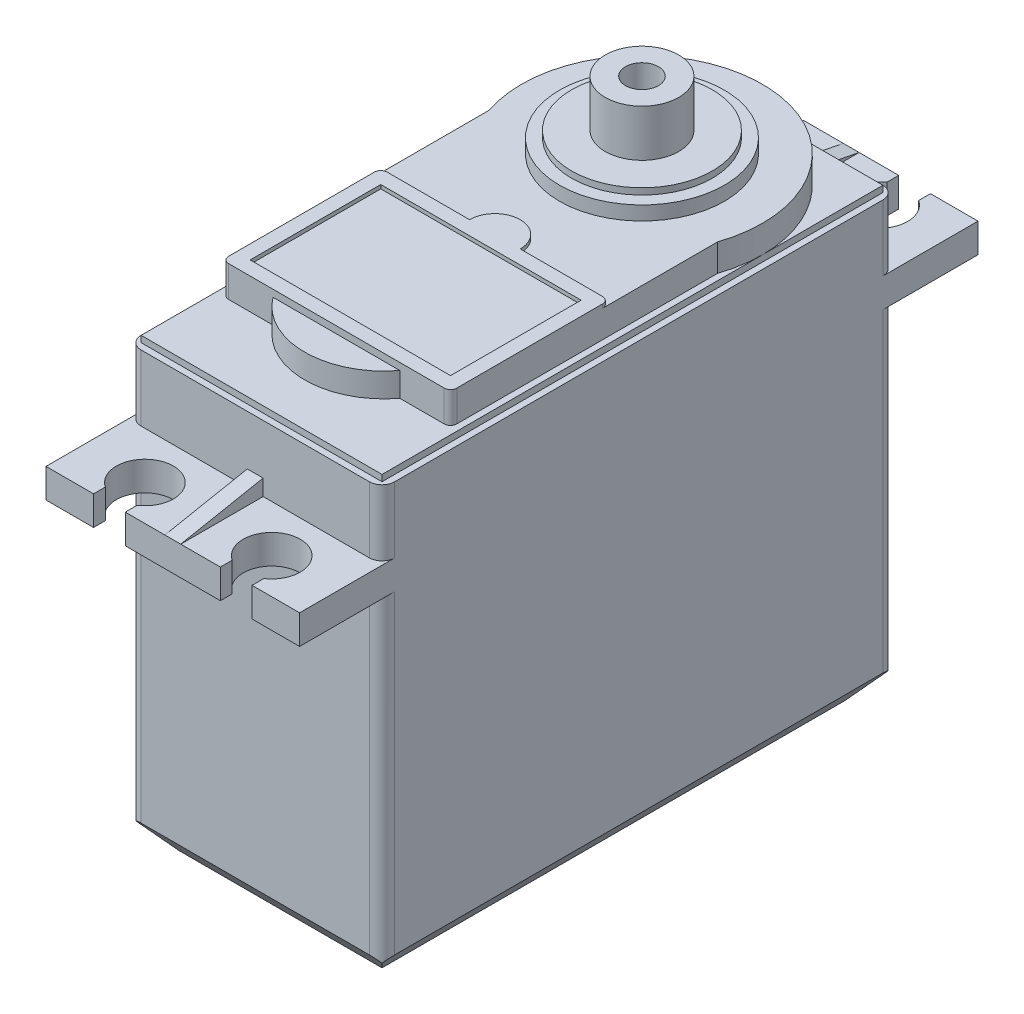
SolidWorks part; units mm, degrees
ref_plane "Front Plane" through (0, 0, 0) normal (0, 0, 1) x (1, 0, 0)
ref_plane "Top Plane" through (0, 0, 0) normal (0, 1, 0) x (1, 0, 0)
ref_plane "Right Plane" through (0, 0, 0) normal (1, 0, 0) x (0, 0, -1)
sketch "Sketch1" plane through (0, 0, 0) normal (0, 1, 0) x (1, 0, 0)
  line L0 (0, 0) -> (0, 10) construction
  line L1 (10, 10) -> (-10, 10)
  line L2 (10, 10) -> (10, -30.5)
  line L3 (10, -30.5) -> (-10, -30.5)
  line L4 (-10, 10) -> (-10, -30.5)
  dimension "D1" = 20
  dimension "D2" = 40.5
  dimension "D3" = 10
extrude "Boss-Extrude1" add sketch "Sketch1" along normal blind 35.2
chamfer "Chamfer1" distance 2 angle 50 4 edges at (0, 0, -10) (-10, 0, 10.25) (0, 0, 30.5) (10, 0, 10.25) first distance on face at (0, 0, 10.25)
ref_plane "Plane1" through (0, 27.2, 0) normal (0, 1, 0) x (-1, 0, 0)
sketch "Sketch2" plane through (0, 27.2, 0) normal (0, 1, 0) x (-1, 0, 0)
  line L0 (-10, 30.5) -> (-10, -10) construction
  line L1 (10, -10) -> (-10, -10)
  line L2 (10, -10) -> (10, -16.5)
  line L3 (10, -16.5) -> (6.25, -16.5)
  line L4 (-10, -10) -> (-10, -16.5)
  line L5 (5, -13.7) -> (-5, -13.7) construction
  line L6 (0, -10) -> (0, -13.7) construction
  line L7 (6.25, -16.5) -> (6.25, -15.5708)
  line L8 (3.75, -16.5) -> (3.75, -15.5708)
  line L9 (-3.75, -15.5708) -> (-3.75, -16.5)
  line L10 (3.75, -16.5) -> (-3.75, -16.5)
  line L11 (-6.25, -15.5708) -> (-6.25, -16.5)
  line L12 (-6.25, -16.5) -> (-10, -16.5)
  line L13 (10, 10.25) -> (-10, 10.25) construction
  line L14 (10, -10) -> (10, 30.5) construction
  line L15 (0, 30.5) -> (0, 34.2) construction
  line L16 (5, 34.2) -> (-5, 34.2) construction
  line L17 (-6.25, 37) -> (-10, 37)
  line L18 (-6.25, 36.0708) -> (-6.25, 37)
  line L19 (3.75, 37) -> (-3.75, 37)
  line L20 (-3.75, 36.0708) -> (-3.75, 37)
  line L21 (3.75, 37) -> (3.75, 36.0708)
  line L22 (6.25, 37) -> (6.25, 36.0708)
  line L23 (-10, 30.5) -> (-10, 37)
  line L24 (10, 37) -> (6.25, 37)
  line L25 (10, 30.5) -> (10, 37)
  line L26 (10, 30.5) -> (-10, 30.5)
  arc A0 (6.25, -15.5708) -> (3.75, -15.5708) centre (5, -13.7) ccw
  arc A1 (-3.75, -15.5708) -> (-6.25, -15.5708) centre (-5, -13.7) ccw
  arc A2 (-3.75, 36.0708) -> (-6.25, 36.0708) centre (-5, 34.2) cw
  arc A3 (6.25, 36.0708) -> (3.75, 36.0708) centre (5, 34.2) cw
  dimension "D2" = 4.5
  dimension "D1" = 10
  dimension "D3" = 2.8
  dimension "D4" = 6.5
  dimension "D5" = 2.5
extrude "Boss-Extrude2" add sketch "Sketch2" along normal blind 2.3
sketch "Sketch3" plane through (0, 29.5, 0) normal (0, 1, 0) x (1, 0, 0)
  line L0 (10, -30.5) -> (-10, -30.5) construction
  line L1 (0.625, -30.5) -> (-0.625, -30.5)
  line L2 (0.625, -30.5) -> (0.625, -37)
  line L3 (0.625, -37) -> (-0.625, -37)
  line L4 (-0.625, -30.5) -> (-0.625, -37)
  line L5 (-3.75, -37) -> (3.75, -37) construction
  line L6 (-10, 10) -> (10, 10) construction
  line L7 (-0.625, 10) -> (0.625, 10)
  line L8 (-0.625, 10) -> (-0.625, 16.5)
  line L9 (-0.625, 16.5) -> (0.625, 16.5)
  line L10 (0.625, 10) -> (0.625, 16.5)
  line L11 (3.75, 16.5) -> (-3.75, 16.5) construction
  line L12 (0, -30.5) -> (0, 0) construction
  line L13 (0, 0) -> (0, 10) construction
  dimension "D1" = 1.25
extrude "Boss-Extrude3" add sketch "Sketch3" along normal blind 1.3
chamfer "Chamfer2" distance 1.3 angle 79 2 edges at (0, 30.8, 37) (0, 30.8, -16.5) first distance on face at (0, 29.25, 37) first distance on face at (0, 29.25, -16.5)
sketch "Sketch5" plane through (0, 35.2, 0) normal (0, 1, 0) x (1, 0, 0)
  line L1 (-9.5, 9.5) -> (9.5, 9.5)
  line L2 (-9.5, 9.5) -> (-9.5, -30)
  line L3 (-9.5, -30) -> (9.5, -30)
  line L4 (9.5, 9.5) -> (9.5, -30)
  line L5 (-10, 10) -> (-9.5, 9.5) construction
  line L6 (10, 10) -> (-10, 10) construction
  line L7 (10, -30.5) -> (9.5, -30) construction
  line L8 (10, 10) -> (9.5, 9.5) construction
  line L9 (10, -30.5) -> (10, 10) construction
  line L10 (-9.5, -30) -> (-10, -30.5) construction
  line L11 (-10, 10) -> (-10, -30.5) construction
  line L13 (-10, -30.5) -> (10, -30.5) construction
  dimension "D1" = 0.5
  dimension "D2" = 0.5
  dimension "D3" = 0.5
  dimension "D4" = 0.5
extrude "Cut-Extrude1" cut sketch "Sketch5" against normal blind 0.5 flip side to cut
sketch "Sketch6" plane through (0, 35.2, 0) normal (0, 1, 0) x (1, 0, 0)
  line L0 (9.5, 9.5) -> (-9.5, 9.5) construction
  line L3 (-9, -3.0414) -> (-9, -24.1)
  line L4 (-9, -24.1) -> (9, -24.1)
  line L5 (9, -3.0414) -> (9, -24.1)
  arc A0 (9, -3.0414) -> (-9, -3.0414) centre (0, 0) ccw
  dimension "D1" = 18
  dimension "D2" = 24.1
extrude "Boss-Extrude4" add sketch "Sketch6" along normal blind 2.15
sketch "Sketch7" plane through (0, 35.2, 0) normal (0, 1, 0) x (1, 0, 0)
  line L0 (-9, -24.1) -> (9, -24.1) construction
  line L1 (-9, -24.1) -> (9, -24.1) construction
  line L2 (-5, -24.1) -> (5, -24.1)
  line L3 (0, -24.1) -> (0, -20.35) construction
  line L4 (0, -20.35) -> (0, 0) construction
  arc A0 (-5, -24.1) -> (5, -24.1) centre (0, -20.35) ccw
  point P8 (0, -26.6)
  dimension "D1" = 10
  dimension "D2" = 2.5
extrude "Boss-Extrude5" add sketch "Sketch7" along normal blind 1.9
sketch "Sketch8" plane through (0, 37.35, 0) normal (0, 1, 0) x (1, 0, 0)
  circle A0 centre (0, 0) radius 6.5
  dimension "D1" = 13
extrude "Boss-Extrude6" add sketch "Sketch8" along normal blind 1.1
sketch "Sketch9" plane through (0, 38.45, 0) normal (0, 1, 0) x (1, 0, 0)
  circle A0 centre (0, 0) radius 5.55
  dimension "D1" = 11.1
extrude "Boss-Extrude7" add sketch "Sketch9" along normal blind 0.5
sketch "Sketch10" plane through (0, 38.95, 0) normal (0, 1, 0) x (1, 0, 0)
  circle A0 centre (0, 0) radius 2.9
  circle A1 centre (0, 0) radius 1.3
  dimension "D1" = 5.8
  dimension "D2" = 2.6
extrude "Boss-Extrude8" add sketch "Sketch10" along normal blind 3.7
sketch "Sketch11" plane through (0, 37.35, 0) normal (0, 1, 0) x (1, 0, 0)
  line L0 (9, -24.1) -> (9, -3.0414) construction
  line L1 (-9, -24.1) -> (9, -24.1)
  line L2 (-9, -24.1) -> (-9, -11.6)
  line L3 (-9, -11.6) -> (-2, -11.6)
  line L4 (9, -24.1) -> (9, -11.6)
  line L5 (0, -11.6) -> (0, 0) construction
  line L6 (-7.9, -23) -> (7.9, -23)
  line L7 (-7.9, -23) -> (-7.9, -12.7)
  line L8 (-7.9, -12.7) -> (7.9, -12.7)
  line L9 (7.9, -23) -> (7.9, -12.7)
  line L10 (2, -11.6) -> (9, -11.6)
  arc A0 (-2, -11.6) -> (2, -11.6) centre (0, -11.6) cw
  dimension "D6" = 2
  dimension "D1" = 1.1
  dimension "D2" = 1.1
  dimension "D3" = 1.1
  dimension "D4" = 1.1
  dimension "D5" = 12.5
extrude "Boss-Extrude9" add sketch "Sketch11" along normal blind 0.3
fillet "Fillet1" radius 0.5 4 edges at (-9, 37.5, 11.6) (9, 37.5, 11.6) (-9, 36.425, 24.1) (9, 36.425, 24.1)
fillet "Fillet2" radius 1 8 edges
